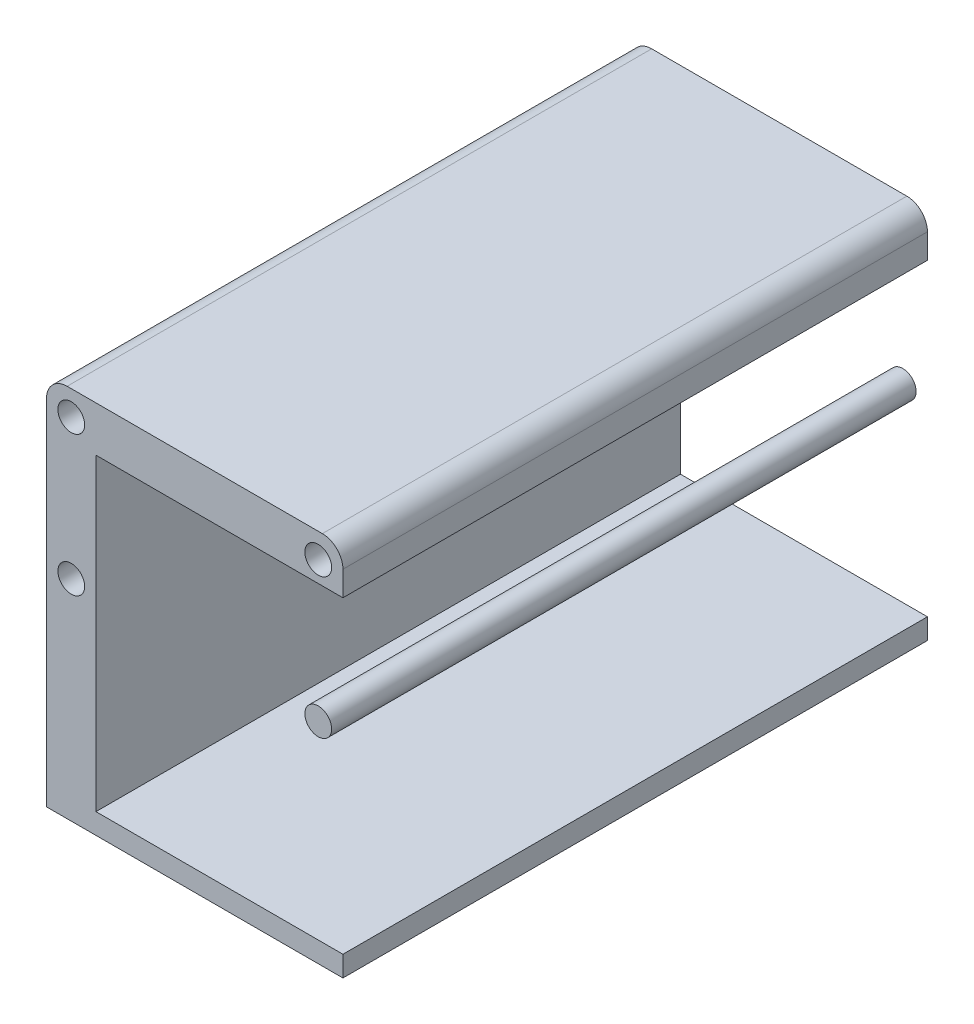
SolidWorks part; units mm, degrees
ref_plane "Plan de face" through (0, 0, 0) normal (0, 0, 1) x (1, 0, 0)
ref_plane "Plan de dessus" through (0, 0, 0) normal (0, 1, 0) x (1, 0, 0)
ref_plane "Plan de droite" through (0, 0, 0) normal (1, 0, 0) x (0, 0, -1)
sketch "Sketch2" plane through (0, 0, 0) normal (0, 0, 1) x (1, 0, 0)
  line L0 (36, 86) -> (36, 1.5833)
  line L8 (31, 91) -> (-31, 91)
  line L9 (-36, 86) -> (-36, 1.5837)
  line L10 (-35.7426, 0) -> (35.7426, 0)
  line L11 (36, 1.5837) -> (36, 5)
  line L12 (36, 5) -> (-24, 5)
  line L13 (-24, 5) -> (-24, 80)
  line L14 (-24, 80) -> (36, 80)
  line L15 (36, 80) -> (36, 86)
  line L16 (31, 91) -> (-31, 91)
  line L18 (-35.7426, 0) -> (35.7426, 0)
  line L119 (-36, 86) -> (-36, 1.5837)
  arc A2 (-31, 91) -> (-36, 86) centre (-31, 86) ccw
  arc A3 (36, 86) -> (31, 91) centre (31, 86) ccw
  arc A5 (36, 86) -> (31, 91) centre (31, 86) ccw
  arc A16 (-31, 91) -> (-36, 86) centre (-31, 86) ccw
  arc A17 (-36, 1.5837) -> (-35.7426, 0) centre (-31, 1.5837) ccw
  arc A18 (-36, 1.5837) -> (-35.7426, 0) centre (-31, 1.5837) ccw
  arc A19 (35.7426, 0) -> (36, 1.5837) centre (31, 1.5837) ccw
  arc A50 (35.7426, 0) -> (36, 1.5837) centre (31, 1.5837) ccw
  dimension "D1" = 0
extrude "Boss-Extrude1" add sketch "Sketch2" along normal blind 5 rebuild error yes
sketch "Sketch3" plane through (0, 0, 5) normal (0, 0, 1) x (1, 0, 0)
  line L3 (31, 91) -> (-31, 91) construction
  line L4 (36, 80) -> (36, 86) construction
  line L5 (-24, 80) -> (36, 80) construction
  line L6 (-24, 5) -> (-24, 80) construction
  line L7 (36, 5) -> (-24, 5) construction
  line L11 (31, 91) -> (-31, 91)
  line L12 (36, 80) -> (36, 86)
  line L13 (-24, 80) -> (36, 80)
  line L14 (-24, 5) -> (-24, 80)
  line L15 (36, 5) -> (-24, 5)
  line L16 (-36, 0) -> (36, 0) construction
  line L17 (-36, 86) -> (-36, 0) construction
  line L18 (-36, 0) -> (36, 0)
  line L19 (-36, 86) -> (-36, 0)
  line L20 (36, 5) -> (36, 0)
  arc A2 (-31, 91) -> (-36, 86) centre (-31, 86) ccw construction
  arc A3 (36, 86) -> (31, 91) centre (31, 86) ccw construction
  arc A6 (-31, 91) -> (-36, 86) centre (-31, 86) ccw
  arc A7 (36, 86) -> (31, 91) centre (31, 86) ccw
  circle A8 centre (30, 51) radius 3.25 construction
  circle A9 centre (30, 85) radius 3.25 construction
  circle A10 centre (-30, 51) radius 3.25 construction
  circle A11 centre (-30, 85) radius 3.25 construction
  circle A12 centre (30, 51) radius 3.25
  circle A13 centre (30, 85) radius 3.25
  circle A14 centre (-30, 51) radius 3.25
  circle A15 centre (-30, 85) radius 3.25
extrude "Boss-Extrude2" add sketch "Sketch3" along normal blind 142
